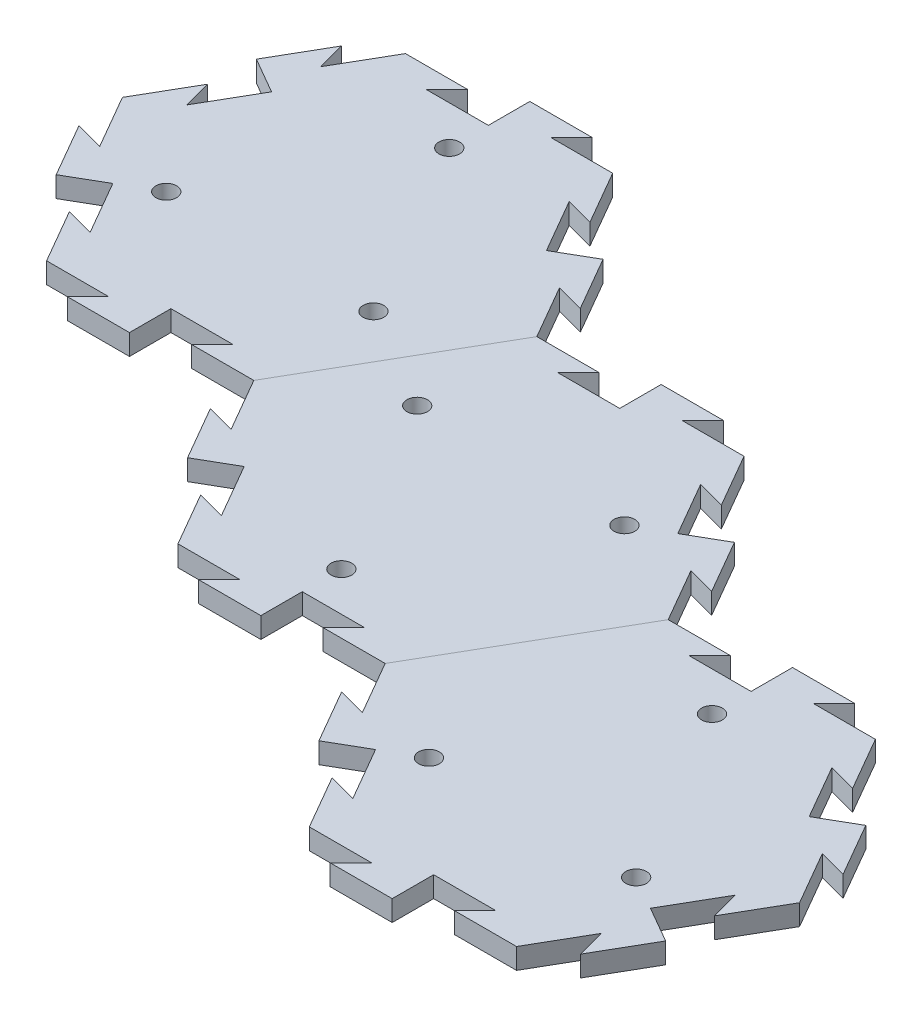
SolidWorks part; units mm, degrees
material "Cedar"
ref_plane "Front Plane" through (0, 0, 0) normal (0, 0, 1) x (1, 0, 0)
ref_plane "Top Plane" through (0, 0, 0) normal (0, 1, 0) x (1, 0, 0)
ref_plane "Right Plane" through (0, 0, 0) normal (1, 0, 0) x (0, 0, -1)
sketch "Sketch1" plane through (0, 0, 0) normal (0, 1, 0) x (1, 0, 0)
  line L0 (0, 0) -> (63.5, 0) construction
  line L1 (63.5, 0) -> (31.75, 54.9926)
  line L2 (31.75, 54.9926) -> (-31.75, 54.9926)
  line L3 (-31.75, 54.9926) -> (-63.5, 0)
  line L4 (-63.5, 0) -> (-31.75, -54.9926)
  line L5 (-31.75, -54.9926) -> (31.75, -54.9926)
  line L6 (31.75, -54.9926) -> (63.5, 0)
  circle A0 centre (0, 0) radius 54.9926 construction
  dimension "D1" = 63.5
extrude "Boss-Extrude1" add sketch "Sketch1" against normal blind 6.35
sketch "Sketch2" plane through (0, 0, 0) normal (0, 1, 0) x (1, 0, 0)
  point P1 (0, 0)
ref_axis "Axis1" through (0, 0, 0) along (0, 1, 0)
sketch "Sketch9" plane through (0, 0, 0) normal (0, 1, 0) x (1, 0, 0)
  line L1 (31.75, -18.3309) -> (0, 36.6617) construction
  line L2 (0, 36.6617) -> (-31.75, -18.3309) construction
  line L3 (-31.75, -18.3309) -> (31.75, -18.3309) construction
  circle A0 centre (0, 0) radius 18.3309 construction
  circle A1 centre (-31.75, -18.3309) radius 3.175
  dimension "D2" = 6.35
  dimension "D1" = 63.5
extrude "Cut-Extrude3" cut sketch "Sketch9" against normal through all
pattern_circular "CirPattern6" count 3 over 360 about axis through (0, 0, 0) along (0, 1, 0) of "Cut-Extrude3"
mirror "Mirror3" about plane through (31.75, -6.35, 54.9926) normal (0.866, 0, 0.5) of bodies 121 125
sketch "Sketch10" plane through (0, 0, 0) normal (0, 1, 0) x (1, 0, 0)
  line L0 (31.75, 54.9926) -> (41.275, 38.4948) construction
  line L1 (41.275, 38.4948) -> (32.6007, 40.8191)
  line L2 (32.6007, 40.8191) -> (42.1257, 24.3213)
  line L3 (42.1257, 24.3213) -> (47.625, 27.4963)
  line L4 (41.275, 38.4948) -> (47.625, 27.4963)
  line L5 (63.5, 0) -> (31.75, 54.9926) construction
  dimension "D1" = 45
  dimension "D2" = 6.35
extrude "Cut-Extrude4" cut sketch "Sketch10" against normal through all
sketch "Sketch11" plane through (0, 0, 0) normal (0, 1, 0) x (1, 0, 0)
  line L0 (47.625, 27.4963) -> (63.5, 0) construction
  line L1 (47.625, 27.4963) -> (53.1243, 30.6713)
  line L2 (53.1243, 30.6713) -> (62.6493, 14.1735)
  line L3 (62.6493, 14.1735) -> (53.975, 16.4978)
  line L4 (53.975, 16.4978) -> (47.625, 27.4963)
  line L5 (53.975, 16.4978) -> (63.5, 0) construction
  line L6 (53.975, 16.4978) -> (63.5, 0) construction
  line L7 (63.5, 0) -> (47.625, 27.4963) construction
  line L8 (31.75, -54.9926) -> (63.5, 0) construction
  dimension "D1" = 45
  dimension "D2" = 6.35
extrude "Boss-Extrude4" add sketch "Sketch11" against normal blind 6.35
pattern_circular "CirPattern7" count 6 over 360 about axis through (0, 0, 0) along (0, 1, 0) skipping 5 of "Cut-Extrude4", "Boss-Extrude4"
mirror "Mirror4" about plane through (158.75, -6.35, 54.9926) normal (0.866, 0, 0.5) of bodies 126 129
sketch "Sketch12" plane through (0, 0, 0) normal (0, 1, 0) x (1, 0, 0)
  line L0 (127, 0) -> (63.5, -109.9852) construction
  point P4 (95.25, -54.9926)
ref_axis "Axis2" through (95.25, 0, 54.9926) along (0, 1, 0)
sketch "Sketch13" plane through (0, 0, 0) normal (0, 1, 0) x (1, 0, 0)
  line L0 (127, 0) -> (136.525, -16.4978) construction
  line L1 (136.525, -16.4978) -> (127.8507, -14.1735)
  line L2 (127.8507, -14.1735) -> (137.3757, -30.6713)
  line L3 (137.3757, -30.6713) -> (142.875, -27.4963)
  line L4 (136.525, -16.4978) -> (142.875, -27.4963)
  line L5 (127, 0) -> (158.75, -54.9926) construction
  dimension "D1" = 45
  dimension "D2" = 6.35
extrude "Cut-Extrude5" cut sketch "Sketch13" against normal through all
sketch "Sketch14" plane through (0, 0, 0) normal (0, 1, 0) x (1, 0, 0)
  line L0 (142.875, -27.4963) -> (158.75, -54.9926) construction
  line L1 (142.875, -27.4963) -> (148.3743, -24.3213)
  line L2 (148.3743, -24.3213) -> (157.8993, -40.8191)
  line L3 (157.8993, -40.8191) -> (149.225, -38.4948)
  line L4 (149.225, -38.4948) -> (142.875, -27.4963)
  line L5 (149.225, -38.4948) -> (158.75, -54.9926) construction
  line L6 (149.225, -38.4948) -> (158.75, -54.9926) construction
  dimension "D1" = 45
  dimension "D2" = 6.35
extrude "Boss-Extrude5" add sketch "Sketch14" against normal blind 6.35
pattern_circular "CirPattern8" count 6 over 360 about axis through (95.25, 0, 54.9926) along (0, 1, 0) skipping 2, 5 of "Cut-Extrude5", "Boss-Extrude5"
sketch "Sketch15" plane through (0, 0, 0) normal (0, 1, 0) x (1, 0, 0)
  line L0 (222.25, -54.9926) -> (158.75, -164.9778) construction
  point P4 (190.5, -109.9852)
ref_axis "Axis3" through (190.5, 0, 109.9852) along (0, 1, 0)
sketch "Sketch16" plane through (0, 0, 0) normal (0, 1, 0) x (1, 0, 0)
  line L0 (222.25, -54.9926) -> (231.775, -71.4904) construction
  line L1 (231.775, -71.4904) -> (223.1007, -69.1661)
  line L2 (223.1007, -69.1661) -> (232.6257, -85.6639)
  line L3 (232.6257, -85.6639) -> (238.125, -82.4889)
  line L4 (231.775, -71.4904) -> (238.125, -82.4889)
  line L5 (254, -109.9852) -> (222.25, -54.9926) construction
  dimension "D1" = 45
  dimension "D2" = 6.35
extrude "Cut-Extrude6" cut sketch "Sketch16" against normal through all
sketch "Sketch17" plane through (0, 0, 0) normal (0, 1, 0) x (1, 0, 0)
  line L0 (238.125, -82.4889) -> (254, -109.9852) construction
  line L1 (238.125, -82.4889) -> (243.6243, -79.3139)
  line L2 (243.6243, -79.3139) -> (253.1493, -95.8117)
  line L3 (253.1493, -95.8117) -> (244.475, -93.4874)
  line L4 (244.475, -93.4874) -> (238.125, -82.4889)
  line L5 (244.475, -93.4874) -> (254, -109.9852) construction
  line L6 (244.475, -93.4874) -> (254, -109.9852) construction
  line L7 (254, -109.9852) -> (238.125, -82.4889) construction
  dimension "D1" = 6.35
  dimension "D2" = 45
extrude "Boss-Extrude6" add sketch "Sketch17" against normal up to surface (6.35 mm away) up to face at (224.9996, -6.35, 126.7286)
pattern_circular "CirPattern9" count 6 over 360 about axis through (190.5, 0, 109.9852) along (0, 1, 0) skipping 2 of "Cut-Extrude6", "Boss-Extrude6"
